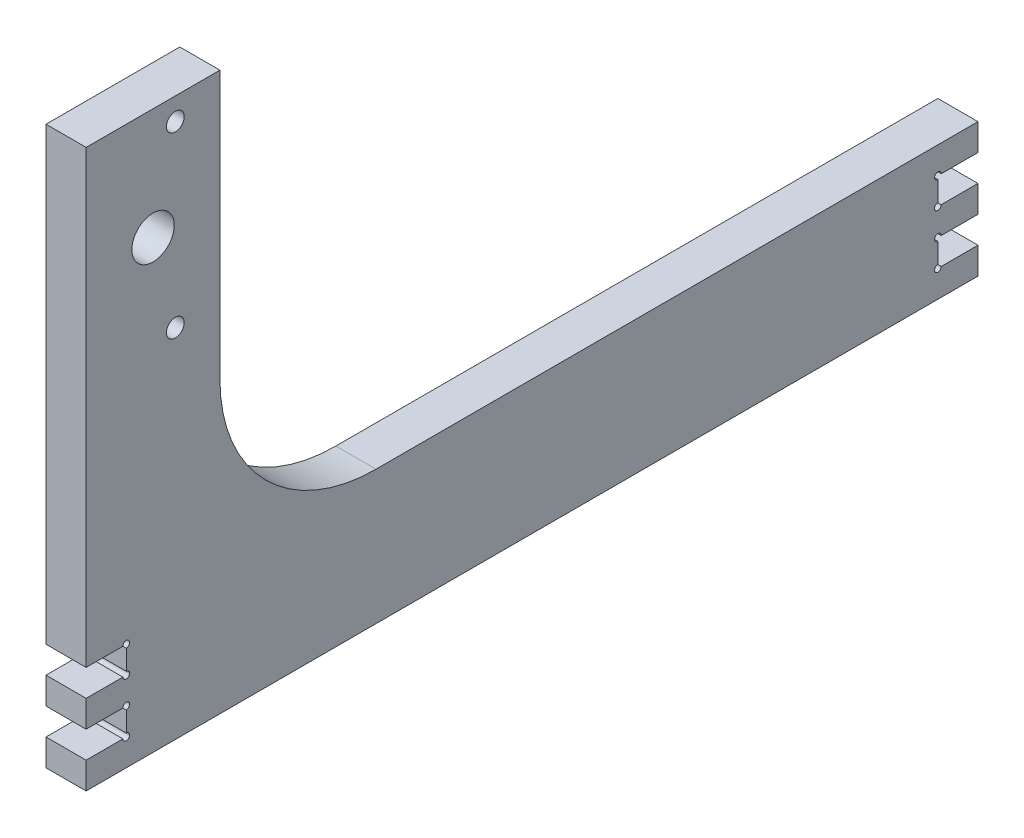
SolidWorks part; units mm, degrees
ref_plane "Front Plane" through (0, 0, 0) normal (0, 0, 1) x (1, 0, 0)
ref_plane "Top Plane" through (0, 0, 0) normal (0, 1, 0) x (1, 0, 0)
ref_plane "Right Plane" through (0, 0, 0) normal (1, 0, 0) x (0, 0, -1)
sketch "Sketch1" plane through (0, 0, 0) normal (1, 0, 0) x (0, 0, -1)
  line L0 (-1000, 0) -> (49000, 0) construction
  line L1 (-30, -250) -> (370, -250)
  line L4 (370, -250) -> (370, -238)
  line L6 (-30, -202) -> (-13.5, -202) construction
  line L7 (0, -1000) -> (0, 49000) construction
  line L9 (-30, 0) -> (-30, -202)
  line L10 (-30, -214) -> (-13.5, -214) construction
  line L11 (-30, -226) -> (-13.5, -226) construction
  line L12 (-30, -238) -> (-13.5, -238) construction
  line L13 (-12, -203.5) -> (-12, -212.5)
  line L14 (-30, -202) -> (-13.5, -202)
  line L15 (-30, -214) -> (-13.5, -214)
  line L16 (-30, -226) -> (-13.5, -226)
  line L17 (-13.5, -238) -> (-30, -238)
  line L20 (0, -750) -> (0, 49250) construction
  line L21 (-12, -227.5) -> (-12, -236.5)
  line L22 (353.5, -238) -> (370, -238)
  line L23 (352, -227.5) -> (352, -236.5)
  line L24 (370, -226) -> (353.5, -226)
  line L25 (370, -214) -> (353.5, -214)
  line L26 (352, -203.5) -> (352, -212.5)
  line L27 (370, -202) -> (353.5, -202)
  line L29 (370, -226) -> (370, -214)
  line L30 (370, -190) -> (370, -202)
  line L31 (30, 0) -> (30, -120)
  line L32 (-30, 0) -> (30, 0)
  line L33 (100, -190) -> (370, -190)
  line L34 (-27.1942, -50) -> (27.1942, -50) construction
  line L35 (-30, -214) -> (-30, -226)
  line L37 (-30, -238) -> (-30, -250)
  line L38 (170, -1250) -> (170, 48750) construction
  line L39 (10, -1000) -> (10, 49000) construction
  circle A1 centre (0, -50) radius 4
  circle A2 centre (10, -90) radius 4
  circle A3 centre (10, -10) radius 4
  arc A5 (100, -190) -> (30, -120) centre (100, -120) cw
  arc A6 (-12, -203.5) -> (-13.5, -202) centre (-12, -202) ccw
  arc A7 (-13.5, -214) -> (-12, -212.5) centre (-12, -214) ccw
  arc A8 (-12, -227.5) -> (-13.5, -226) centre (-12, -226) ccw
  arc A9 (-13.5, -238) -> (-12, -236.5) centre (-12, -238) ccw
  arc A10 (353.5, -202) -> (352, -203.5) centre (352, -202) ccw
  arc A11 (352, -212.5) -> (353.5, -214) centre (352, -214) ccw
  arc A12 (353.5, -226) -> (352, -227.5) centre (352, -226) ccw
  arc A13 (352, -236.5) -> (353.5, -238) centre (352, -238) ccw
  point P0 (0, 0)
  point P51 (0, -50)
  point P52 (170, -250)
  point P59 (0, 0)
  point P63 (0, 0)
  point P64 (0, 0)
  point P65 (0, 0)
  point P66 (0, 0)
  dimension "D7" = 48
  dimension "D14" = 8
  dimension "D16" = 40
  dimension "D18" = 120
  dimension "D12" = 70
  dimension "D13" = 100
  dimension "D20" = 3
  dimension "D25" = 3
  dimension "D2" = 12
  dimension "D3" = 18
  dimension "D4" = 60
  dimension "D5" = 250
  dimension "D6" = 400
  dimension "D8" = 250
  dimension "D9" = 12
  dimension "D11" = 60
  dimension "D10" = 9
  dimension "D15" = 50
  dimension "D17" = 40
  dimension "D19" = 30
  dimension "D21" = 4
  dimension "D22" = 9
  dimension "D23" = 12
  dimension "D24" = 18
  dimension "D27" = 16.5
  dimension "D28" = 200
  dimension "D29" = 18
  dimension "D30" = 40
  dimension "D26" = 4
extrude "Boss-Extrude1" add sketch "Sketch1" along normal blind 18 contours L33 A5 L31 L32 L9 L14 L13 L15 L35 L16 L21 L17 L1 L4 L22 L23 L24 L29 L25 L26 L27 L30 A1 A2 A3 region at (0, -244, 25.283)
sketch "Sketch3" plane through (18, 0, 0) normal (1, 0, 0) x (0, 0, -1)
  circle A0 centre (0, -50) radius 9.5
  dimension "D1" = 19
extrude "Cut-Extrude1" cut sketch "Sketch3" against normal up to next
